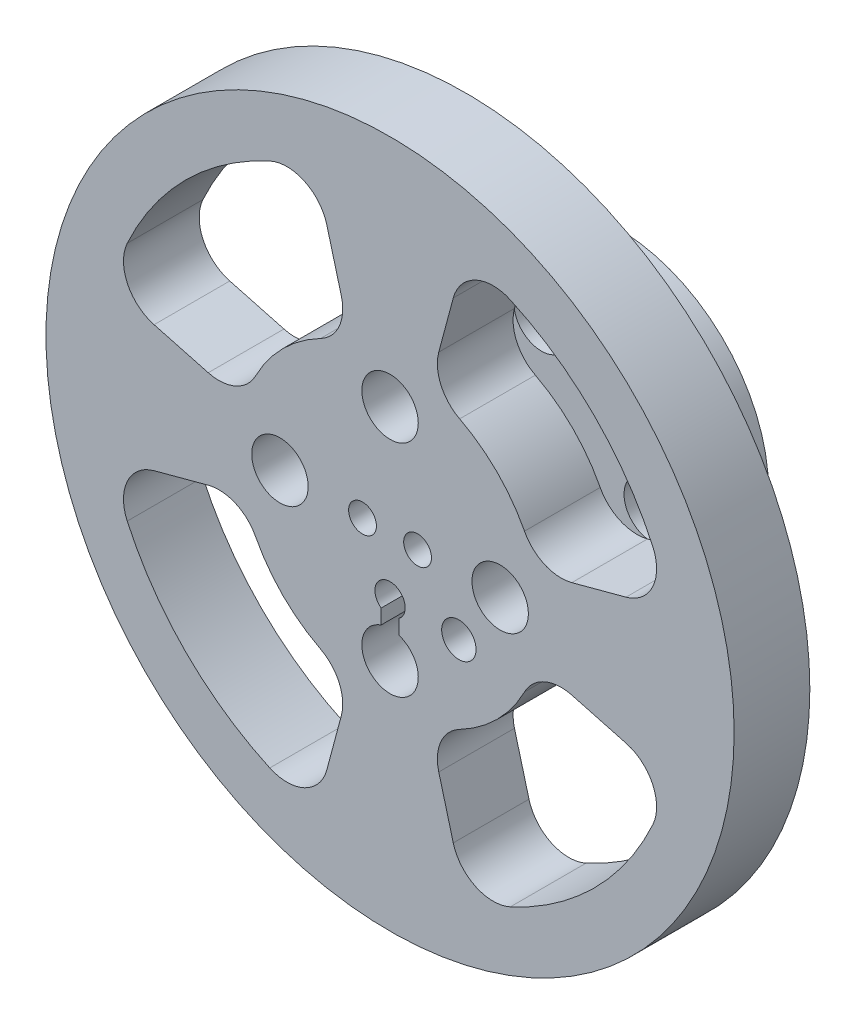
SolidWorks part; units mm, degrees
material "ﾎﾟﾘｵｷｼﾒﾁﾚﾝ(POM)ｱｾﾀｰﾙ共重合体"
ref_plane "正面" through (0, 0, 0) normal (0, 0, 1) x (1, 0, 0)
ref_plane "平面" through (0, 0, 0) normal (0, 1, 0) x (1, 0, 0)
ref_plane "右側面" through (0, 0, 0) normal (1, 0, 0) x (0, 0, -1)
sketch "ｽｹｯﾁ1" plane through (0, 0, 0) normal (0, 0, 1) x (1, 0, 0)
  line L0 (0, 0) -> (-8, 0) construction
  circle A0 centre (-8, 0) radius 1.15
  circle A1 centre (0, 8) radius 1.15
  circle A2 centre (8, 0) radius 1.15
  circle A3 centre (0, -8) radius 1.15
  circle A4 centre (0, 0) radius 11
  circle A5 centre (0, 0) radius 3 construction
  point P13 (0, 0)
  dimension "D1" = 2.3
  dimension "D4" = 22
  dimension "D5" = 6
  dimension "D2" = 8
  dimension "D3" = 4
extrude "ﾎﾞｽ - 押し出し1" add sketch "ｽｹｯﾁ1" along normal blind 5.5
sketch "ｽｹｯﾁ2" plane through (0, 0, 5.5) normal (0, 0, 1) x (1, 0, 0)
  circle A0 centre (0, 0) radius 3
  dimension "D1" = 6
extrude "ﾎﾞｽ - 押し出し2" add sketch "ｽｹｯﾁ2" along normal blind 5.5 separate body
sketch "ｽｹｯﾁ3" plane through (0, 0, 11) normal (0, 0, 1) x (1, 0, 0)
  line L0 (0, 0) -> (0, 25) construction
  line L1 (3.5393, 13.2088) -> (4.5936, 17.1435)
  line L2 (17.6777, 17.6777) -> (0, 0) construction
  line L3 (13.2088, 3.5393) -> (17.1435, 4.5936)
  line L4 (13.2088, -3.5393) -> (17.1435, -4.5936)
  line L5 (3.5393, -13.2088) -> (4.5936, -17.1435)
  line L6 (-3.5393, -13.2088) -> (-4.5936, -17.1435)
  line L7 (-13.2088, -3.5393) -> (-17.1435, -4.5936)
  line L8 (-13.2088, 3.5393) -> (-17.1435, 4.5936)
  line L9 (-3.5393, 13.2088) -> (-4.5936, 17.1435)
  arc A0 (5.0577, 9.7683) -> (9.7683, 5.0577) centre (0, 0) cw
  circle A1 centre (0, 0) radius 11 construction
  circle A2 centre (0, 0) radius 25
  arc A3 (8.7399, 19.0949) -> (19.0949, 8.7399) centre (0, 0) cw
  arc A4 (0, 11) -> (2.847, 10.6252) centre (0, 0) cw construction
  arc A5 (3.5393, 13.2088) -> (5.0577, 9.7683) centre (6.4371, 12.4324) ccw
  circle A10 centre (-8, 0) radius 2.05
  circle A11 centre (0, 8) radius 2.05
  circle A12 centre (8, 0) radius 2.05
  circle A13 centre (0, -8) radius 2.05
  arc A14 (4.5936, 17.1435) -> (8.7399, 19.0949) centre (7.4914, 16.367) cw
  arc A15 (13.2088, 3.5393) -> (9.7683, 5.0577) centre (12.4324, 6.4371) cw
  arc A16 (17.1435, 4.5936) -> (19.0949, 8.7399) centre (16.367, 7.4914) ccw
  arc A17 (3.5393, -13.2088) -> (5.0577, -9.7683) centre (6.4371, -12.4324) cw
  arc A18 (9.7683, -5.0577) -> (5.0577, -9.7683) centre (0, 0) cw
  arc A19 (13.2088, -3.5393) -> (9.7683, -5.0577) centre (12.4324, -6.4371) ccw
  arc A20 (17.1435, -4.5936) -> (19.0949, -8.7399) centre (16.367, -7.4914) cw
  arc A21 (19.0949, -8.7399) -> (8.7399, -19.0949) centre (0, 0) cw
  arc A22 (4.5936, -17.1435) -> (8.7399, -19.0949) centre (7.4914, -16.367) ccw
  arc A23 (-13.2088, -3.5393) -> (-9.7683, -5.0577) centre (-12.4324, -6.4371) cw
  arc A24 (-5.0577, -9.7683) -> (-9.7683, -5.0577) centre (0, 0) cw
  arc A25 (-3.5393, -13.2088) -> (-5.0577, -9.7683) centre (-6.4371, -12.4324) ccw
  arc A26 (-4.5936, -17.1435) -> (-8.7399, -19.0949) centre (-7.4914, -16.367) cw
  arc A27 (-8.7399, -19.0949) -> (-19.0949, -8.7399) centre (0, 0) cw
  arc A28 (-17.1435, -4.5936) -> (-19.0949, -8.7399) centre (-16.367, -7.4914) ccw
  arc A29 (-3.5393, 13.2088) -> (-5.0577, 9.7683) centre (-6.4371, 12.4324) cw
  arc A30 (-9.7683, 5.0577) -> (-5.0577, 9.7683) centre (0, 0) cw
  arc A31 (-13.2088, 3.5393) -> (-9.7683, 5.0577) centre (-12.4324, 6.4371) ccw
  arc A32 (-17.1435, 4.5936) -> (-19.0949, 8.7399) centre (-16.367, 7.4914) cw
  arc A33 (-19.0949, 8.7399) -> (-8.7399, 19.0949) centre (0, 0) cw
  arc A34 (-4.5936, 17.1435) -> (-8.7399, 19.0949) centre (-7.4914, 16.367) ccw
  point P14 (0, 0)
  point P70 (0, 0)
  dimension "D2" = 4.1
  dimension "D1" = 50
  dimension "D4" = 10
  dimension "D7" = 3
  dimension "D5" = 45
  dimension "D6" = 30
  dimension "D3" = 4
  dimension "D8" = 4
extrude "ﾎﾞｽ - 押し出し3" add sketch "ｽｹｯﾁ3" along normal blind 5.5 separate body
sketch "ｽｹｯﾁ8" plane through (0, 0, 16.5) normal (0, 0, 1) x (1, 0, 0)
  line L0 (0, 3) -> (0, 0) construction
  line L1 (0, 0) -> (-2, 0) construction
  circle A0 centre (0, 0) radius 3 construction
  circle A1 centre (-2, 0) radius 1.01
  circle A2 centre (2, 0) radius 1.01
  dimension "D1" = 6
  dimension "D2" = 2
  dimension "D3" = 2.02
extrude "ｶｯﾄ - 押し出し4" cut sketch "ｽｹｯﾁ8" against normal up to surface (11 mm away) up to face at (9.15, 0, 5.5)
sketch "ｽｹｯﾁ9" plane through (0, 0, 5.5) normal (0, 0, 1) x (1, 0, 0)
  circle A0 centre (-2, 0) radius 0.8
  circle A1 centre (2, 0) radius 0.8
  dimension "D1" = 1.6
extrude "ｶｯﾄ - 押し出し5" cut sketch "ｽｹｯﾁ9" against normal up to surface (5.5 mm away) up to face at (11, 0, 0)
sketch "ｽｹｯﾁ11" plane through (0, 0, 16.5) normal (0, 0, 1) x (1, 0, 0)
  line L0 (-2, 0) -> (2, 0) construction
  line L1 (-2, 2.5) -> (2, 2.5)
  line L2 (-2, -2.5) -> (2, -2.5)
  arc A0 (-2, 2.5) -> (-2, -2.5) centre (-2, 0) ccw
  arc A1 (2, -2.5) -> (2, 2.5) centre (2, 0) ccw
  point P4 (0, 0)
  dimension "D1" = 2.5
extrude "ｶｯﾄ - 押し出し6" [suppressed] cut sketch "ｽｹｯﾁ11" against normal offset from surface 12 and the other way blind 2.5
sketch "ｽｹｯﾁ12" plane through (0, 0, 5.5) normal (0, 0, 1) x (1, 0, 0)
  circle A0 centre (-8, 0) radius 2
  circle A1 centre (0, 8) radius 2
  circle A2 centre (8, 0) radius 2
  circle A3 centre (0, -8) radius 2
  circle A4 centre (0, 8) radius 1.15 construction
  point P11 (0, 0)
  dimension "D1" = 4
  dimension "D2" = 4
extrude "ｶｯﾄ - 押し出し7" cut sketch "ｽｹｯﾁ12" against normal blind 2.5
sketch "ｽｹｯﾁ13" plane through (0, 0, 16.5) normal (0, 0, 1) x (1, 0, 0)
  line L0 (0, 0) -> (0, -4.1) construction
  arc A0 (-2.995, -0.1736) -> (2.995, -0.1736) centre (0, 0) ccw construction
  arc A1 (-2.995, -0.1736) -> (2.995, -0.1736) centre (0, 0) ccw construction
  circle A2 centre (0, -4.1) radius 1.1
  dimension "D1" = 2.2
extrude "ｶｯﾄ - 押し出し8" cut sketch "ｽｹｯﾁ13" against normal up to surface (5.5 mm away) up to face at (-0.99, 0, 11)
sketch "ｽｹｯﾁ14" plane through (0, 0, 16.5) normal (0, 0, 1) x (1, 0, 0)
  line L1 (-0.65, -4.9874) -> (0.65, -4.9874)
  line L2 (-0.65, -4.9874) -> (-0.65, -6.0558)
  line L3 (-0.65, -6.0558) -> (0.65, -6.0558)
  line L4 (0.65, -4.9874) -> (0.65, -6.0558)
  circle A0 centre (0, -4.1) radius 1.1 construction
  circle A1 centre (0, -8) radius 2.05 construction
  circle A2 centre (4.9997, -4.1537) radius 3.5 construction
  arc A4 (2.995, 0.1736) -> (-2.995, 0.1736) centre (0, 0) ccw construction
  arc A5 (2.995, 0.1736) -> (-2.995, 0.1736) centre (0, 0) ccw construction
  arc A6 (-2.995, -0.1736) -> (2.995, -0.1736) centre (0, 0) ccw construction
  arc A7 (-2.995, -0.1736) -> (2.995, -0.1736) centre (0, 0) ccw construction
  circle A8 centre (4.9997, -4.1537) radius 1.25
  dimension "D2" = 7
  dimension "D3" = 2.5
  dimension "D4" = 5
  dimension "D1" = 1.3
extrude "ｶｯﾄ - 押し出し9" cut sketch "ｽｹｯﾁ14" against normal up to surface (5.5 mm away) up to face at (1.1, -4.1, 11)
